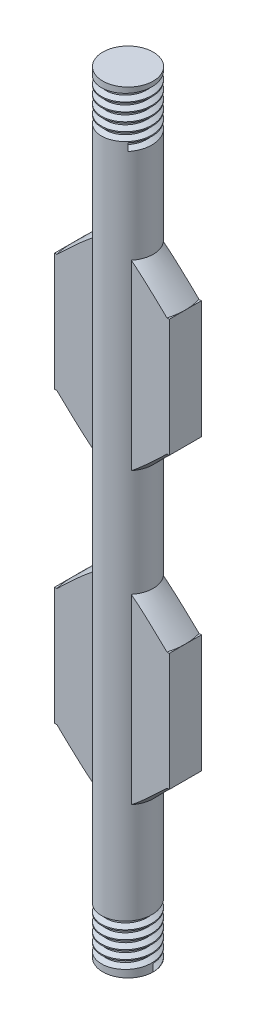
SolidWorks part; units mm, degrees
ref_plane "Front Plane" through (0, 0, 0) normal (0, 0, 1) x (1, 0, 0)
ref_plane "Top Plane" through (0, 0, 0) normal (0, 1, 0) x (1, 0, 0)
ref_plane "Right Plane" through (0, 0, 0) normal (1, 0, 0) x (0, 0, -1)
sketch "Sketch1" plane through (0, 0, 0) normal (0, 1, 0) x (1, 0, 0)
  circle A0 centre (0, 0) radius 2.35
  dimension "D1" = 4.7
extrude "Boss-Extrude1" add sketch "Sketch1" along normal blind 14
extrude "Boss-Extrude2" add sketch "Sketch1<2>" along normal blind 3 from surface starting at face at (0, 14, 2.35)
sketch "Sketch1<2>" plane through (0, 0, 0) normal (0, 1, 0) x (1, 0, 0) same geometry as "Sketch1"
sketch "Sketch2" plane through (0, 17, 0) normal (0, 1, 0) x (1, 0, 0)
  line L0 (-1.809, -1.5) -> (-5.35, -1.5)
  line L1 (-5.35, -1.5) -> (-5.35, 1.5)
  line L2 (-5.35, 1.5) -> (-1.809, 1.5)
  line L3 (0, 2.35) -> (0, -2.35) construction
  line L4 (-2.35, 0) -> (-5.35, 0) construction
  line L5 (0, 0) -> (-2.35, 0) construction
  line L6 (5.35, 1.5) -> (1.809, 1.5)
  line L7 (5.35, -1.5) -> (5.35, 1.5)
  line L8 (1.809, -1.5) -> (5.35, -1.5)
  arc A0 (-1.809, 1.5) -> (-2.35, 0) centre (0, 0) ccw construction
  circle A1 centre (0, 0) radius 2.35
  arc A2 (-1.809, -1.5) -> (1.809, -1.5) centre (0, 0) ccw
  arc A3 (-2.35, 0) -> (-1.809, -1.5) centre (0, 0) ccw construction
  arc A4 (1.809, 1.5) -> (-1.809, 1.5) centre (0, 0) ccw
  arc A5 (1.809, -1.5) -> (1.809, 1.5) centre (0, 0) ccw construction
  point P10 (0, 0)
  point P11 (0, 0)
  point P12 (-5.35, 0)
  dimension "D2" = 3
  dimension "D3" = 3
  dimension "D1" = 0
extrude "Boss-Extrude3" add sketch "Sketch2" along normal blind 11
extrude "Boss-Extrude4" add sketch "Sketch1<3>" along normal blind 16 from surface starting at face at (0, 28, 0)
sketch "Sketch1<3>" plane through (0, 0, 0) normal (0, 1, 0) x (1, 0, 0) same geometry as "Sketch1"
extrude "Boss-Extrude5" add sketch "Sketch2<2>" along normal blind 11 from surface starting at face at (0, 44, 2.35)
sketch "Sketch2<2>" plane through (0, 17, 0) normal (0, 1, 0) x (1, 0, 0) same geometry as "Sketch2"
extrude "Boss-Extrude6" add sketch "Sketch1<4>" along normal blind 3 from surface starting at face at (0, 55, 0)
sketch "Sketch1<4>" plane through (0, 0, 0) normal (0, 1, 0) x (1, 0, 0) same geometry as "Sketch1"
extrude "Boss-Extrude7" add sketch "Sketch1<5>" along normal blind 14 from surface starting at face at (0, 58, 2.35)
sketch "Sketch1<5>" plane through (0, 0, 0) normal (0, 1, 0) x (1, 0, 0) same geometry as "Sketch1"
chamfer "Chamfer1" distance 3 angle 45 8 edges at (2.35, 55, 0) (-2.35, 55, 0) (-2.35, 44, 0) (2.35, 44, 0) (2.35, 28, 0) (-2.35, 28, 0) (-2.35, 17, 0) (2.35, 17, 0)
thread "Thread1" pitch 0.8 method cut profile "Thread Profile1" start angle 0, offset 0, length 4.5, pitch 0.8, diameter 4.7
ref_plane "Plane1" through (-2.35, 72, 0) normal (0, 0, 1) x (-1, 0, 0)
sketch "Thread Profile1" plane through (-2.35, 72, 0) normal (0, 0, 1) x (-1, 0, 0)
  line L0 (0, 0) -> (0, 0.8) construction
  line L11 (0, 0) -> (0, 0.7)
  line L12 (0, 0.7) -> (-0.433, 0.45)
  line L13 (-0.433, 0.45) -> (-0.433, 0.25)
  line L15 (-0.433, 0.25) -> (0, 0)
  line L17 (-0.433, 0.35) -> (0, 0.35) construction
  point P2 (0, 0)
  dimension "Pitch" = 0.8
  dimension "Profile_Angle" = 60
  dimension "Profile_Land" = 0.2
  dimension "Profile_Height" = 0.433
thread "Thread2" pitch 0.8 method cut profile "Thread Profile2" start angle 0, offset 0, length 4.5, pitch 0.8, diameter 4.7
ref_plane "Plane2" through (2.35, 0, 0) normal (0, 0, 1) x (1, 0, 0)
sketch "Thread Profile2" plane through (2.35, 0, 0) normal (0, 0, 1) x (1, 0, 0)
  line L0 (0, 0) -> (0, 0.8) construction
  line L11 (0, 0) -> (0, 0.7)
  line L12 (0, 0.7) -> (-0.433, 0.45)
  line L13 (-0.433, 0.45) -> (-0.433, 0.25)
  line L15 (-0.433, 0.25) -> (0, 0)
  line L17 (-0.433, 0.35) -> (0, 0.35) construction
  point P2 (0, 0)
  dimension "Pitch" = 0.8
  dimension "Profile_Angle" = 60
  dimension "Profile_Land" = 0.2
  dimension "Profile_Height" = 0.433
